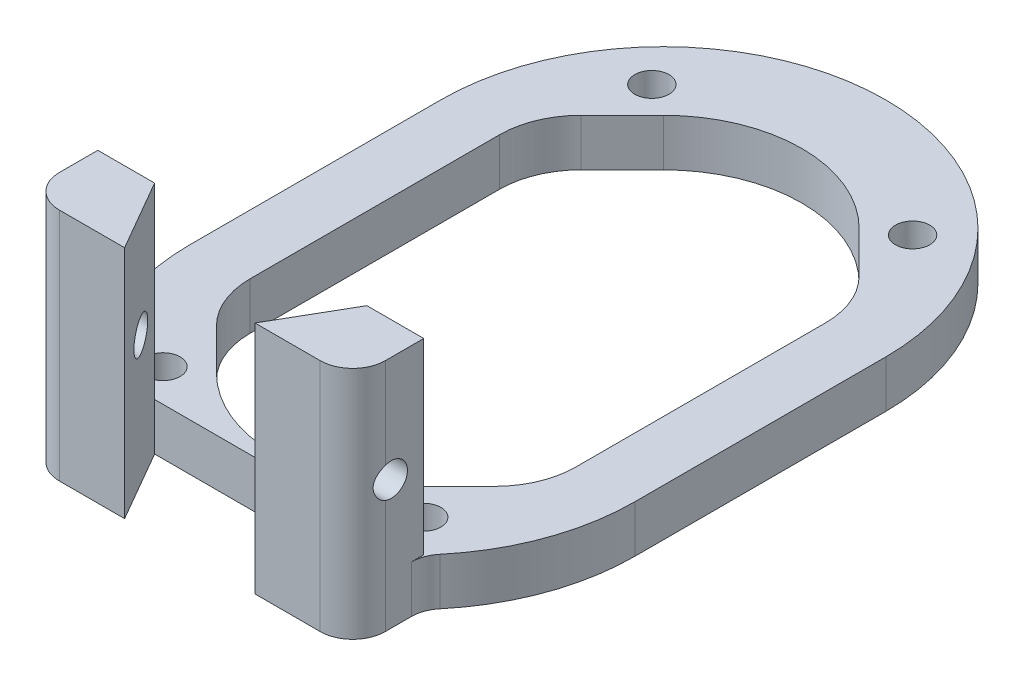
SolidWorks part; units mm, degrees
ref_plane "Front Plane" through (0, 0, 0) normal (0, 0, 1) x (1, 0, 0)
ref_plane "Top Plane" through (0, 0, 0) normal (0, 1, 0) x (1, 0, 0)
ref_plane "Right Plane" through (0, 0, 0) normal (1, 0, 0) x (0, 0, -1)
sketch "Outline" plane through (0, 0, 0) normal (0, 1, 0) x (1, 0, 0)
  line L1 (10, -17) -> (-10, -17)
  line L2 (10, -17) -> (10, 17)
  line L3 (10, 17) -> (-10, 17)
  line L4 (-10, -17) -> (-10, 17)
  line L5 (10, -17) -> (-10, 17) construction
  line L6 (10, 17) -> (-10, -17) construction
  point P0 (0, 0)
  dimension "D1" = 20
  dimension "D2" = 34
sketch "MountingHoles" plane through (0, 0, 0) normal (0, 1, 0) x (1, 0, 0)
  line L1 (8, -15) -> (-8, -15)
  line L2 (8, -15) -> (8, 15)
  line L3 (8, 15) -> (-8, 15)
  line L4 (-8, -15) -> (-8, 15)
  line L5 (8, -15) -> (-8, 15) construction
  line L6 (8, 15) -> (-8, -15) construction
  circle A0 centre (-8, 15) radius 1.05
  circle A1 centre (8, 15) radius 1.05
  circle A2 centre (-8, -15) radius 1.05
  circle A3 centre (8, -15) radius 1.05
  point P8 (0, 0)
  dimension "D1" = 2.1
  dimension "D2" = 30
  dimension "D3" = 16
sketch "Horn" plane through (0, 0, 0) normal (0, 1, 0) x (1, 0, 0)
  line L0 (10, 17) -> (-10, 17) construction
  line L3 (0, -1000) -> (0, 49000) construction
  line L4 (10, 17) -> (-10, -17) construction
  circle A0 centre (0, 7.7) radius 8
  point P17 (0, 0)
  dimension "D1" = 16
  dimension "D2" = 9.3
sketch "WireCutout" plane through (0, 0, 0) normal (0, 1, 0) x (1, 0, 0)
  line L0 (-10, -17) -> (-10, 17) construction
  line L1 (-10, -7.15) -> (-5.8, -7.15)
  line L2 (-10, -7.15) -> (-10, 4.15)
  line L3 (-10, 4.15) -> (-5.8, 4.15)
  line L4 (-5.8, -7.15) -> (-5.8, 4.15)
  line L5 (10, -17) -> (10, 17) construction
  line L6 (10, 4.15) -> (5.8, 4.15)
  line L7 (10, 4.15) -> (10, -7.15)
  line L8 (10, -7.15) -> (5.8, -7.15)
  line L9 (5.8, 4.15) -> (5.8, -7.15)
  line L10 (10, 17) -> (-10, 17) construction
  line L11 (10, -17) -> (-10, -17) construction
  dimension "D1" = 12.85
  dimension "D2" = 9.85
  dimension "D3" = 4.2
sketch "Sketch26" plane through (0, 0, 0) normal (0, 1, 0) x (1, 0, 0)
  line L0 (0, -201000) -> (0, 249000) construction
  line L1 (-1000, 0) -> (49000, 0) construction
  line L2 (-13.6561, -7.7) -> (-13.6561, 7.7)
  line L3 (-8.5, 7.7) -> (-8.5, -7.7)
  line L4 (8.5, -7.7) -> (8.5, 7.7)
  line L5 (13.6561, 7.7) -> (13.6561, -7.7)
  arc A0 (-13.6561, 7.7) -> (13.6561, 7.7) centre (0, 7.7) cw
  arc A1 (-8.5, 7.7) -> (8.5, 7.7) centre (0, 7.7) cw
  arc A2 (-13.6561, -7.7) -> (13.6561, -7.7) centre (0, -7.7) ccw
  arc A3 (-8.5, -7.7) -> (8.5, -7.7) centre (0, -7.7) ccw
  circle A4 centre (0, 7.7) radius 8 construction
  point P0 (0, -7.7)
  dimension "D1" = 0.5
extrude "Boss-Extrude6" add sketch "Sketch26" along normal blind 2.9
sketch "Sketch27" plane through (0, 2.9, 0) normal (0, 1, 0) x (1, 0, 0)
  circle A0 centre (-8, 15) radius 1.05
  circle A1 centre (8, 15) radius 1.05
  circle A2 centre (8, -15) radius 1.05
  circle A3 centre (-8, -15) radius 1.05
  circle A4 centre (-8, -15) radius 1.05 construction
  circle A5 centre (8, -15) radius 1.05 construction
  circle A6 centre (8, 15) radius 1.05 construction
  circle A7 centre (-8, 15) radius 1.05 construction
extrude "Cut-Extrude12" cut sketch "Sketch27" against normal through all
sketch "Sketch29" plane through (0, 2.9, 0) normal (0, 1, 0) x (1, 0, 0)
  line L0 (-10, -17) -> (10, -17)
  line L1 (-996.0655, -21.3561) -> (49003.9345, -21.3561) construction
  line L2 (-10, -17) -> (-10, -21.3561)
  line L3 (10, -17) -> (10, -21.3561)
  line L4 (10, -21.3561) -> (-10, -21.3561)
  arc A2 (-13.6561, -7.7) -> (13.6561, -7.7) centre (0, -7.7) ccw construction
extrude "Boss-Extrude8" add sketch "Sketch29" along normal blind 11.5 and the other way up to surface (2.9 mm away) other way up to face at (-8, 0, 16.05)
sketch "Sketch30" plane through (0, 14.4, 0) normal (0, 1, 0) x (1, 0, 0)
  line L0 (-4, -21.3561) -> (-6.515, -17)
  line L1 (-10, -21.3561) -> (10, -21.3561) construction
  line L2 (10, -17) -> (-10, -17) construction
  line L3 (-6.515, -17) -> (6.515, -17)
  line L4 (6.515, -17) -> (4, -21.3561)
  line L5 (4, -21.3561) -> (-4, -21.3561)
  line L9 (0, -201000) -> (0, 249000) construction
  dimension "D1" = 60
  dimension "D2" = 60
  dimension "D3" = 4
  dimension "D4" = 4
extrude "Cut-Extrude13" cut sketch "Sketch30" against normal through all
fillet "Fillet1" radius 2 4 edges at (-10, 7.2, 21.3561) (10, 7.2, 21.3561) (10, 1.45, 17) (-10, 1.45, 17)
sketch "Sketch31" plane through (-10, 0, 0) normal (-1, 0, 0) x (0, 0, 1)
  line L0 (17, 2.9) -> (17, 14.4) construction
  line L2 (17.7556, 0) -> (19.3561, 0) construction
  circle A0 centre (19, 7.9) radius 1
  dimension "D1" = 2
  dimension "D3" = 7.9
  dimension "D2" = 2
extrude "Cut-Extrude14" cut sketch "Sketch31" against normal through all and the other way through all
sketch "Sketch34" plane through (0, 2.9, 0) normal (0, 1, 0) x (1, 0, 0)
  line L0 (-10, 9.7208) -> (-6.0104, 13.7104)
  line L1 (-10, 9.7208) -> (-10, -9.7208)
  line L2 (-10, -9.7208) -> (-6.0104, -13.7104)
  line L3 (-6.0104, 13.7104) -> (-6.0104, -13.7104)
  line L5 (-10, -17) -> (-10, 17) construction
  arc A1 (-8.5, -7.7) -> (8.5, -7.7) centre (0, -7.7) ccw construction
  arc A2 (8.5, 7.7) -> (-8.5, 7.7) centre (0, 7.7) ccw construction
  dimension "D1" = 45
extrude "Cut-Extrude16" cut sketch "Sketch34" against normal blind 10
fillet "Fillet3" radius 5 2 edges at (-10, 1.45, 9.7208) (-10, 1.45, -9.7208)
mirror "Mirror2" about plane through (0, 0, 0) normal (1, 0, 0) of "Fillet3", "Cut-Extrude16"
